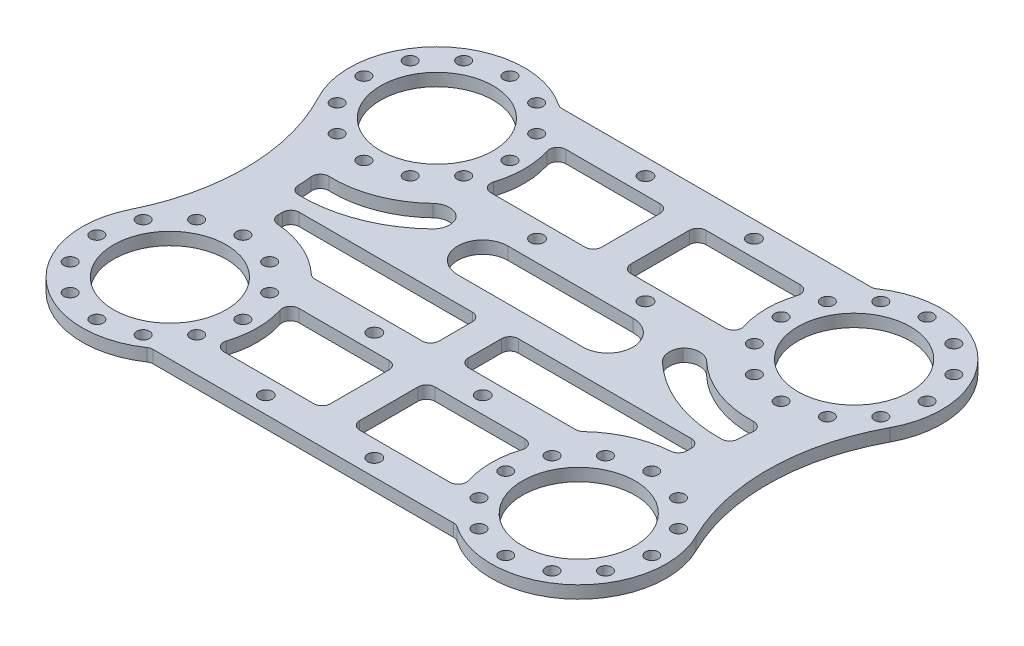
SolidWorks part; units mm, degrees
material "Thornel Mat VMA"
ref_plane "前视基准面" through (0, 0, 0) normal (0, 0, 1) x (1, 0, 0)
ref_plane "上视基准面" through (0, 0, 0) normal (0, 1, 0) x (1, 0, 0)
ref_plane "右视基准面" through (0, 0, 0) normal (1, 0, 0) x (0, 0, -1)
other "Configuration Table"
sketch "草图1" plane through (0, 0, 0) normal (0, 1, 0) x (1, 0, 0)
  line L0 (-50, 0) -> (50, 0) construction
  line L1 (-50, 21) -> (50, 21)
  line L2 (-50, -21) -> (50, -21)
  line L3 (0, -32.5) -> (0, 32.763) construction
  line L4 (-87.3644, -32.5) -> (86.7644, -32.5) construction
  line L5 (-49, -65) -> (49, -65) construction
  line L6 (-49, -44) -> (49, -44)
  line L7 (-49, -86) -> (49, -86)
  arc A0 (-50, 21) -> (-50, -21) centre (-50, 0) ccw
  arc A1 (50, -21) -> (50, 21) centre (50, 0) ccw
  circle A2 centre (-50, 0) radius 13.5
  circle A3 centre (-50, 17.5) radius 1.525
  circle A4 centre (-13, 13) radius 1.6
  circle A5 centre (-13, -13) radius 1.6
  circle A6 centre (-41.25, 15.1554) radius 1.525
  circle A7 centre (-34.8446, 8.75) radius 1.525
  circle A8 centre (-32.5, 0) radius 1.525
  circle A9 centre (-34.8446, -8.75) radius 1.525
  circle A10 centre (-41.25, -15.1554) radius 1.525
  circle A11 centre (-50, -17.5) radius 1.525
  circle A12 centre (-58.75, -15.1554) radius 1.525
  circle A13 centre (-65.1554, -8.75) radius 1.525
  circle A14 centre (-67.5, 0) radius 1.525
  circle A15 centre (-65.1554, 8.75) radius 1.525
  circle A16 centre (-58.75, 15.1554) radius 1.525
  circle A17 centre (58.75, 15.1554) radius 1.525
  circle A18 centre (65.1554, 8.75) radius 1.525
  circle A19 centre (67.5, 0) radius 1.525
  circle A20 centre (65.1554, -8.75) radius 1.525
  circle A21 centre (58.75, -15.1554) radius 1.525
  circle A22 centre (50, -17.5) radius 1.525
  circle A23 centre (41.25, -15.1554) radius 1.525
  circle A24 centre (34.8446, -8.75) radius 1.525
  circle A25 centre (32.5, 0) radius 1.525
  circle A26 centre (41.25, 15.1554) radius 1.525
  circle A27 centre (13, -13) radius 1.6
  circle A28 centre (13, 13) radius 1.6
  circle A29 centre (50, 17.5) radius 1.525
  circle A30 centre (50, 0) radius 13.5
  circle A31 centre (34.8446, 8.75) radius 1.525
  circle A32 centre (-49, -65) radius 13.5
  circle A33 centre (49, -65) radius 13.5
  arc A34 (-49, -44) -> (-49, -86) centre (-49, -65) ccw
  arc A35 (49, -86) -> (49, -44) centre (49, -65) ccw
  circle A36 centre (-49, -82.5) radius 1.525
  circle A37 centre (-57.75, -80.1554) radius 1.525
  circle A38 centre (-64.1554, -73.75) radius 1.525
  circle A39 centre (-66.5, -65) radius 1.525
  circle A40 centre (-64.1554, -56.25) radius 1.525
  circle A41 centre (-57.75, -49.8446) radius 1.525
  circle A42 centre (-49, -47.5) radius 1.525
  circle A43 centre (-40.25, -49.8446) radius 1.525
  circle A44 centre (-33.8446, -56.25) radius 1.525
  circle A45 centre (-31.5, -65) radius 1.525
  circle A46 centre (-33.8446, -73.75) radius 1.525
  circle A47 centre (-40.25, -80.1554) radius 1.525
  circle A48 centre (64.1554, -56.25) radius 1.525
  circle A49 centre (66.5, -65) radius 1.525
  circle A50 centre (64.1554, -73.75) radius 1.525
  circle A51 centre (57.75, -80.1554) radius 1.525
  circle A52 centre (49, -82.5) radius 1.525
  circle A53 centre (40.25, -80.1554) radius 1.525
  circle A54 centre (33.8446, -73.75) radius 1.525
  circle A55 centre (31.5, -65) radius 1.525
  circle A56 centre (33.8446, -56.25) radius 1.525
  circle A57 centre (40.25, -49.8446) radius 1.525
  circle A58 centre (49, -47.5) radius 1.525
  circle A59 centre (57.75, -49.8446) radius 1.525
  circle A60 centre (13, -52) radius 1.6
  circle A61 centre (-13, -52) radius 1.6
  circle A62 centre (13, -78) radius 1.6
  circle A63 centre (-13, -78) radius 1.6
  arc A64 (68.5201, -9.8999) -> (67.8158, -55.6745) centre (112.6154, -33.471) ccw
  arc A65 (-68.5201, -9.8999) -> (-67.8158, -55.6745) centre (-112.6154, -33.471) cw
  point P2 (0, 0)
  point P40 (-50, 0)
  point P67 (50, 0)
  point P78 (0, -65)
  point P113 (-49, -65)
  dimension "D2" = 21
  dimension "D3" = 27
  dimension "D5" = 3.05
  dimension "D9" = 3.2
  dimension "D13" = 100
  dimension "D1" = 100
  dimension "D4" = 17.5
  dimension "D6" = 26
  dimension "D7" = 13
  dimension "D8" = 13
  dimension "D11" = 32.5
  dimension "D14" = 98
  dimension "D15" = 17.5
  dimension "D10" = 12
  dimension "D12" = 12
extrude "凸台-拉伸1" add sketch "草图1" along normal blind 3 contours L2 A1 L1 A0 A30 A28 A26 A24 A22 A20 A18 A2 A3 A4 A5 A6 A7 A8 A9 A10 A11 A12 A13 A14 A15 A16 | L7 A35 L6 A34 A59 A58 A57 A56 A55 A54 A53 A52 A51 A50 A49 A48 A46 A44 A42 A40 A38 A36 A32 A33 A37 A39 | A35 A1 L2 A0 A34 L6 region at (0, 0, 0) region at (0, 0, 32.5194) region at (0, 0, 65)
sketch "草图2" plane through (0, 0, 0) normal (0, 1, 0) x (1, 0, 0)
  circle A0 centre (0, 0) radius 5
  dimension "D1" = 10
extrude "切除-拉伸3" cut sketch "草图2" along normal blind 10
sketch "草图4" plane through (0, 3, 0) normal (0, 1, 0) x (1, 0, 0)
  line L0 (50, 0) -> (37.3012, -29.9164) construction
  line L1 (50, 0) -> (50, -57.0343) construction
  line L2 (0, -62.6667) -> (0, 37.526) construction
  line L3 (-50, 0) -> (-50, -57.0343) construction
  line L4 (-50, 0) -> (-37.3012, -29.9164) construction
  line L5 (0, -20.6143) -> (0, -65.6143) construction
  line L6 (5, -20.6143) -> (5, -65.6143)
  line L7 (-5, -20.6143) -> (-5, -65.6143)
  line L8 (100, 0) -> (0, -38.3864) construction
  arc A0 (29.9133, -14.8837) -> (53.247, -24.7882) centre (50, 0) ccw
  arc A1 (24.8743, -20.6143) -> (52.6251, -32.3938) centre (50, 0) ccw
  arc A2 (53.247, -24.7882) -> (52.6251, -32.3938) centre (112.6154, -33.471) ccw
  arc A4 (68.5201, -9.8999) -> (67.8158, -55.6745) centre (112.6154, -33.471) ccw construction
  arc A5 (29.9133, -14.8837) -> (24.8743, -20.6143) centre (-17.5734, 21.7909) cw
  arc A6 (-29.9133, -14.8837) -> (-24.8743, -20.6143) centre (17.5734, 21.7909) ccw
  arc A7 (-53.247, -24.7882) -> (-52.6251, -32.3938) centre (-112.6154, -33.471) cw
  arc A8 (-24.8743, -20.6143) -> (-52.6251, -32.3938) centre (-50, 0) cw
  arc A9 (-29.9133, -14.8837) -> (-53.247, -24.7882) centre (-50, 0) cw
  arc A10 (5, -20.6143) -> (-5, -20.6143) centre (0, -20.6143) ccw
  arc A11 (-5, -65.6143) -> (5, -65.6143) centre (0, -65.6143) ccw
  circle A14 centre (49, -65) radius 21 construction
  arc A15 (49, -86) -> (67.8158, -55.6745) centre (49, -65) ccw construction
  point P28 (0, -43.1143)
  dimension "D1" = 50
  dimension "D2" = 65
  dimension "D3" = 10
  dimension "D5" = 5
  dimension "D8" = 100
  dimension "D4" = 23
  dimension "D6" = 45
  dimension "D9" = 69
sketch "草图5" plane through (0, 3, 0) normal (0, 1, 0) x (1, 0, 0)
  line L0 (31.0263, 9) -> (-31.0263, 9)
  line L1 (0, 0) -> (14.0031, 0) construction
  line L2 (31.0263, -9) -> (-31.0263, -9)
  line L3 (-37.6712, 17) -> (37.6712, 17)
  line L4 (-50, 21) -> (50, 21) construction
  line L5 (-50, 21) -> (50, 21)
  line L6 (-36.6712, -82) -> (36.6712, -82)
  line L7 (-30.0263, -74) -> (30.0263, -74)
  line L8 (-30.0263, -56) -> (30.0263, -56)
  line L9 (-49, -86) -> (49, -86) construction
  line L10 (-49, -86) -> (49, -86)
  arc A0 (-31.0263, -9) -> (-31.0263, 9) centre (-50, 0) ccw
  arc A1 (50, 21) -> (37.6712, 17) centre (50, 0) ccw
  circle A2 centre (13, 13) radius 1.6 construction
  circle A3 centre (-13, 13) radius 1.6 construction
  arc A4 (31.0263, 9) -> (31.0263, -9) centre (50, 0) ccw
  arc A5 (-37.6712, 17) -> (-50, 21) centre (-50, 0) ccw
  arc A6 (-49, -86) -> (-36.6712, -82) centre (-49, -65) ccw
  arc A7 (30.0263, -56) -> (30.0263, -74) centre (49, -65) ccw
  circle A8 centre (49, -65) radius 21 construction
  circle A9 centre (13, -78) radius 1.6 construction
  circle A10 centre (13, -52) radius 1.6 construction
  arc A11 (-30.0263, -74) -> (-30.0263, -56) centre (-49, -65) ccw
  arc A12 (36.6712, -82) -> (49, -86) centre (49, -65) ccw
  dimension "D1" = 4
  dimension "D2" = 4
  dimension "D3" = 4
  dimension "D4" = 4
  dimension "D5" = 4
extrude "切除-拉伸4" cut sketch "草图5" against normal blind 10
sketch "草图6" plane through (0, 3, 0) normal (0, 1, 0) x (1, 0, 0)
  line L0 (-32.0589, -48) -> (32.0589, -48)
  line L2 (-15, -24) -> (15, -24) construction
  line L3 (-15, -18) -> (15, -18)
  line L4 (-15, -30) -> (15, -30)
  line L5 (49, -41) -> (49, -36)
  line L6 (49, -36) -> (-49, -36)
  line L7 (-49, -36) -> (-49, -41)
  arc A0 (24.8743, -20.6143) -> (52.6251, -32.3938) centre (50, 0) ccw construction
  arc A1 (53.247, -24.7882) -> (52.6251, -32.3938) centre (112.6154, -33.471) ccw construction
  arc A2 (29.9133, -14.8837) -> (53.247, -24.7882) centre (50, 0) ccw construction
  arc A3 (24.8743, -20.6143) -> (29.9133, -14.8837) centre (-17.5734, 21.7909) ccw construction
  arc A4 (-52.6251, -32.3938) -> (-53.247, -24.7882) centre (-112.6154, -33.471) ccw construction
  arc A5 (-52.6251, -32.3938) -> (-24.8743, -20.6143) centre (-50, 0) ccw construction
  arc A6 (-29.9133, -14.8837) -> (-24.8743, -20.6143) centre (17.5734, 21.7909) ccw construction
  arc A7 (-53.247, -24.7882) -> (-29.9133, -14.8837) centre (-50, 0) ccw construction
  arc A8 (24.8743, -20.6143) -> (52.6251, -32.3938) centre (50, 0) ccw
  arc A9 (53.247, -24.7882) -> (52.6251, -32.3938) centre (112.6154, -33.471) ccw
  arc A10 (29.9133, -14.8837) -> (53.247, -24.7882) centre (50, 0) ccw
  arc A11 (24.8743, -20.6143) -> (29.9133, -14.8837) centre (-17.5734, 21.7909) ccw
  arc A12 (-52.6251, -32.3938) -> (-53.247, -24.7882) centre (-112.6154, -33.471) ccw
  arc A13 (-52.6251, -32.3938) -> (-24.8743, -20.6143) centre (-50, 0) ccw
  arc A14 (-29.9133, -14.8837) -> (-24.8743, -20.6143) centre (17.5734, 21.7909) ccw
  arc A15 (-53.247, -24.7882) -> (-29.9133, -14.8837) centre (-50, 0) ccw
  arc A16 (-32.0589, -48) -> (-49, -41) centre (-49, -65) ccw
  arc A17 (49, -41) -> (32.0589, -48) centre (49, -65) ccw
  circle A18 centre (13, -52) radius 1.6 construction
  arc A19 (-15, -18) -> (-15, -30) centre (-15, -24) ccw
  arc A20 (15, -30) -> (15, -18) centre (15, -24) ccw
  circle A21 centre (-49, -65) radius 13.5 construction
  circle A22 centre (-49, -65) radius 13.5 construction
  circle A23 centre (49, -65) radius 21 construction
  circle A24 centre (13, -13) radius 1.6 construction
  point P30 (0, -24)
  dimension "D1" = 48
  dimension "D4" = 6
  dimension "D2" = 4
  dimension "D3" = 5
  dimension "D5" = 30
  dimension "D6" = 12
extrude "切除-拉伸5" cut sketch "草图6" against normal blind 10
fillet "圆角1" radius 2 18 edges at (-31.0263, 1.5, 9) (-31.0263, 1.5, -9) (31.0263, 1.5, -9) (31.0263, 1.5, 9) (30.0263, 1.5, 56) (30.0263, 1.5, 74) (-30.0263, 1.5, 74) (-30.0263, 1.5, 56) (53.247, 1.5, 24.7882) (52.6251, 1.5, 32.3938) (-53.247, 1.5, 24.7882) (-52.6251, 1.5, 32.3938) (32.0589, 1.5, 48) (-32.0589, 1.5, 48) (-49, 1.5, 41) (-49, 1.5, 36) (49, 1.5, 41) (49, 1.5, 36)
fillet "圆角2" radius 4 4 edges at (24.8743, 1.5, 20.6143) (29.9133, 1.5, 14.8837) (-24.8743, 1.5, 20.6143) (-29.9133, 1.5, 14.8837)
sketch "草图7" plane through (0, 3, 0) normal (0, 1, 0) x (1, 0, 0)
  line L0 (0, -36) -> (0, -48)
  line L1 (47, -36) -> (-47, -36) construction
  line L2 (-31.2518, -48) -> (31.2518, -48) construction
  line L3 (0, -56) -> (0, -74)
  line L4 (27.0911, -56) -> (-27.0911, -56) construction
  line L5 (-27.0911, -74) -> (27.0911, -74) construction
  line L6 (0, 9) -> (0, -9)
  line L7 (28.0911, 9) -> (-28.0911, 9) construction
  line L8 (-28.0911, -9) -> (28.0911, -9) construction
extrude "拉伸-薄壁1" add sketch "草图7" against normal blind 3 thin thin type mid plane wall 7
fillet "圆角3" radius 2 16 edges at (3.5, 1.5, -9) (3.5, 1.5, 9) (-3.5, 1.5, 74) (-3.5, 1.5, 56) (-3.5, 1.5, 48) (-3.5, 1.5, 36) (3.5, 1.5, 48) (3.5, 1.5, 36) (3.5, 1.5, 74) (-3.5, 1.5, -9) (-3.5, 1.5, 9) (3.5, 1.5, 56) (36.6712, 1.5, 82) (37.6712, 1.5, -17) (-37.6712, 1.5, -17) (-36.6712, 1.5, 82)
